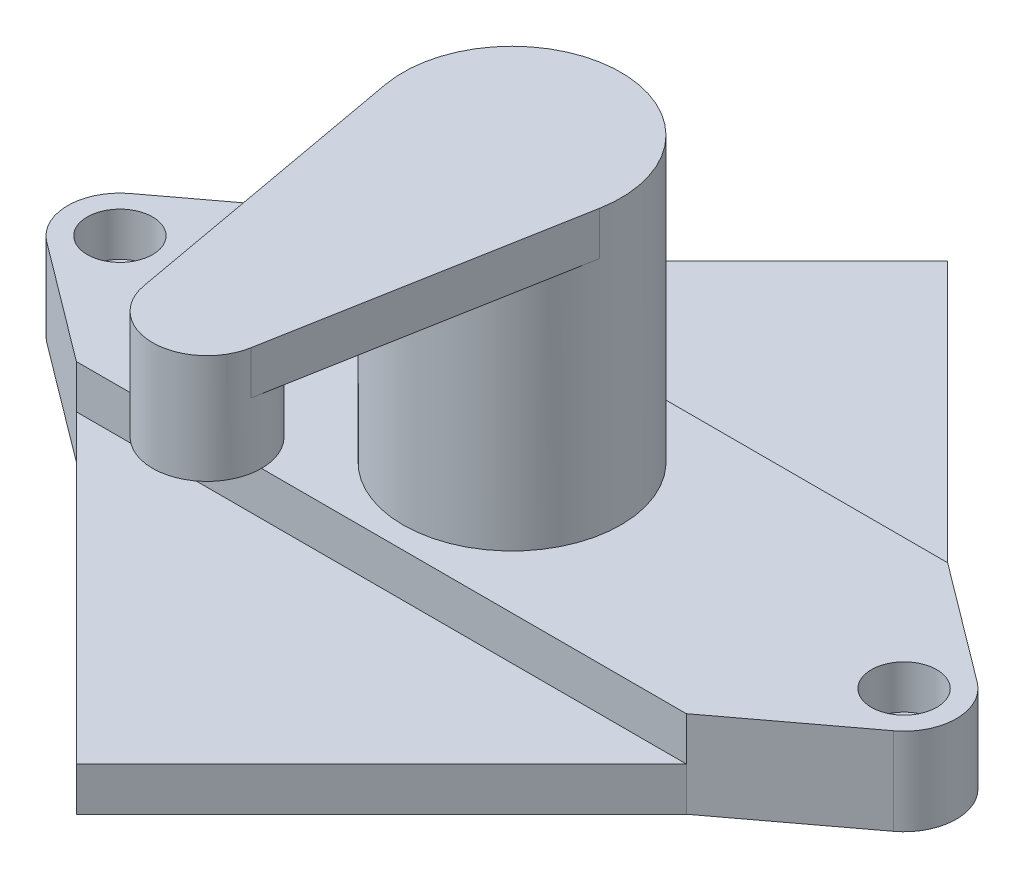
SolidWorks part; units mm, degrees
ref_plane "Alzado" through (0, 0, 0) normal (0, 0, 1) x (1, 0, 0)
ref_plane "Planta" through (0, 0, 0) normal (0, 1, 0) x (1, 0, 0)
ref_plane "Vista lateral" through (0, 0, 0) normal (1, 0, 0) x (0, 0, -1)
sketch "Croquis2" plane through (0, 0, 0) normal (0, 1, 0) x (1, 0, 0)
  line L0 (-97.2, 9.6) -> (-70, 30)
  line L1 (-70, -30) -> (70, -30)
  line L2 (-70, -30) -> (-70, 30) construction
  line L3 (-70, 30) -> (70, 30)
  line L4 (70, -30) -> (70, 30) construction
  line L5 (-70, -30) -> (70, 30) construction
  line L6 (-70, 30) -> (70, -30) construction
  line L7 (70, 30) -> (97.2, 9.6)
  line L8 (97.2, -9.6) -> (70, -30)
  line L9 (-97.2, -9.6) -> (-70, -30)
  line L10 (-70, 30) -> (0, 100)
  line L11 (0, 100) -> (70, 30)
  line L12 (-70, -30) -> (0, -100)
  line L13 (0, -100) -> (70, -30)
  circle A0 centre (0, 0) radius 25
  arc A1 (97.2, -9.6) -> (97.2, 9.6) centre (90, 0) ccw
  arc A2 (-97.2, 9.6) -> (-97.2, -9.6) centre (-90, 0) ccw
  point P0 (0, 0)
  point P14 (0, 0)
  dimension "D1" = 90
  dimension "D3" = 24
  dimension "D4" = 24
  dimension "D5" = 50
  dimension "D2" = 60
  dimension "D6" = 90
  dimension "D7" = 100
  dimension "D8" = 100
extrude "Saliente-Extruir1" add sketch "Croquis2" along normal blind 10 contours L12 L13 L1 | L11 L10 L3 region at (0, 0, -53.3333) region at (0, 0, 53.3333)
extrude "Saliente-Extruir2" add sketch "Croquis2<3>" along normal blind 20 contours L0 A2 L9 L1 L8 A1 L7 L3 A0 region at (-82.3242, 0, -18.0989)
sketch "Croquis2<3>" plane through (0, 0, 0) normal (0, 1, 0) x (1, 0, 0) same geometry as "Croquis2"
extrude "Saliente-Extruir3" add sketch "Croquis2<4>" along normal blind 85 contours A0 region at (0, 0, 0)
sketch "Croquis2<4>" plane through (0, 0, 0) normal (0, 1, 0) x (1, 0, 0) same geometry as "Croquis2"
sketch "Croquis3" plane through (0, 85, 0) normal (0, 1, 0) x (1, 0, 0)
  line L0 (-24.5982, -4.4643) -> (-12.2991, -72.2321)
  line L1 (24.5982, -4.4643) -> (12.2991, -72.2321)
  circle A0 centre (0, 0) radius 25 construction
  circle A1 centre (0, 0) radius 25 construction
  circle A2 centre (0, -70) radius 12.5
  point P11 (0, 0)
  point P12 (0, -80.0558)
  circle M5 centre (0, 0) radius 25
  dimension "D1" = 25
  dimension "D2" = 70
extrude "Saliente-Extruir4" add sketch "Croquis3" against normal blind 10 contours A2 L1 L0 M5 region at (0, 85, 39.3989)
extrude "Saliente-Extruir5" add sketch "Croquis3<3>" against normal blind 25 contours A2 region at (0, 85, 70)
sketch "Croquis3<3>" plane through (0, 85, 0) normal (0, 1, 0) x (1, 0, 0) same geometry as "Croquis3"
hole_wizard "Avellanado para tornillo con cabeza ovalada de #01" positions "Croquis4" profile "Croquis6" countersink size "#0" standard "Ansi Inch" end condition through all
sketch "Croquis4" plane through (0, 20, 0) normal (0, 1, 0) x (1, 0, 0)
  point P0 (90, 0)
  point P2 (-90, 0)
  point P10 (49.4585, -0.8383)
  point P14 (0, 0)
  point P15 (0, 0)
  dimension "D1" = 90
  dimension "D2" = 90
sketch "Croquis6" plane through (90, 20, 0) normal (1, 0, 0) x (0, 0, 1)
  line L0 (0, 0) -> (0, 20)
  line L1 (0, 20) -> (3.5, 20)
  line L2 (3.5, 20) -> (3.5, 14.6015)
  line L3 (3.5, 14.6015) -> (7.5, 10)
  line L4 (7.5, 10) -> (7.5, 0)
  line L6 (7.5, 0) -> (0, 0)
  line L7 (-3.5, 14.6015) -> (-7.5, 10) construction
  line L11 (0, -6.35) -> (0, 107.95) construction
  dimension "Diámetro de taladro hasta el siguiente" = 7
  dimension "Profundidad de taladro hasta el siguiente" = 20
  dimension "Diámetro de avellanado" = 15
  dimension "Ángulo de avellanado" = 82
  dimension "Espacio libre" = 10
